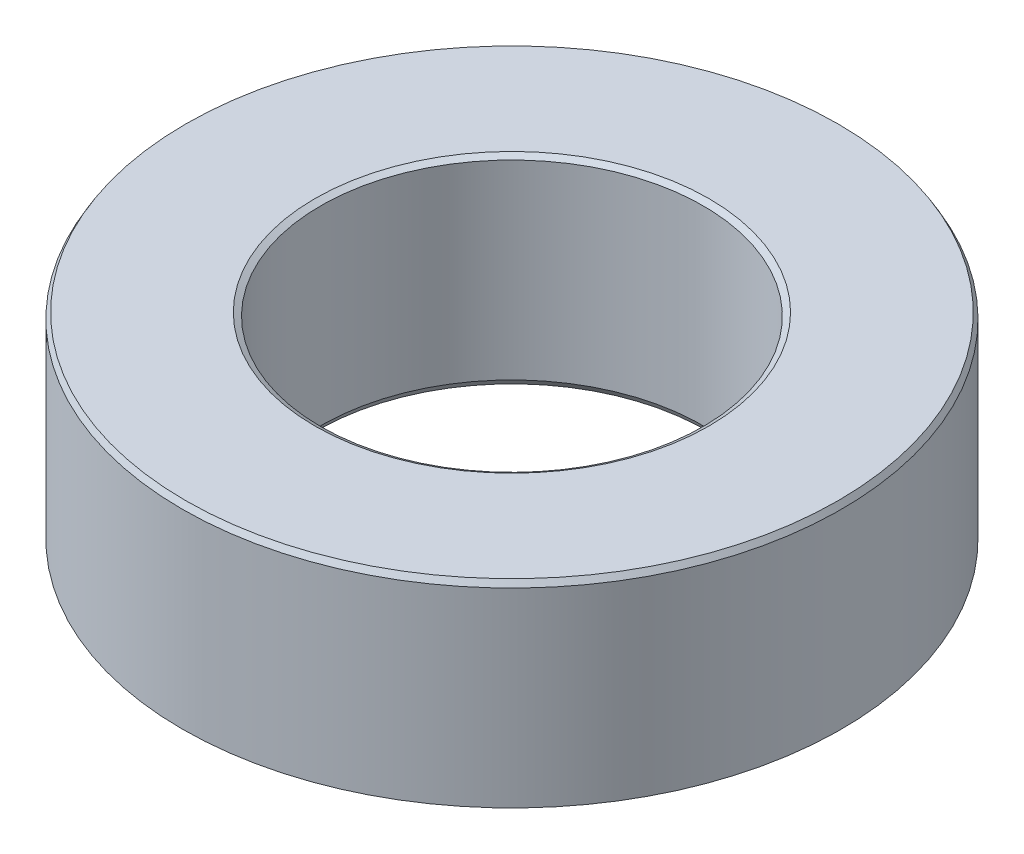
SolidWorks part; units mm, degrees
ref_plane "Front Plane" through (0, 0, 0) normal (0, 0, 1) x (1, 0, 0)
ref_plane "Top Plane" through (0, 0, 0) normal (0, 1, 0) x (1, 0, 0)
ref_plane "Right Plane" through (0, 0, 0) normal (1, 0, 0) x (0, 0, -1)
sketch "Sketch1" plane through (0, 0, 0) normal (0, 1, 0) x (1, 0, 0)
  circle A0 centre (0, 0) radius 50
  dimension "SLEEVE_OD" = 100
extrude "Boss-Extrude1" add sketch "Sketch1" along normal blind 30.2769
sketch "Sketch2" plane through (0, 0, 0) normal (0, 1, 0) x (1, 0, 0)
  circle A0 centre (0, 0) radius 29.0156
  dimension "BORE_D" = 58.0311
extrude "Cut-Extrude1" cut sketch "Sketch2" along normal through all
chamfer "Chamfer1" distance 0.8764 angle 30 4 edges at (0, 30.2769, 29.0156) (0, 0, 29.0156) (0, 0, 50) (0, 30.2769, 50) first distance on face at (0, 30.2769, 29.0156) first distance on face at (0, 0, 29.0156) first distance on face at (0, 30.2769, 50)
